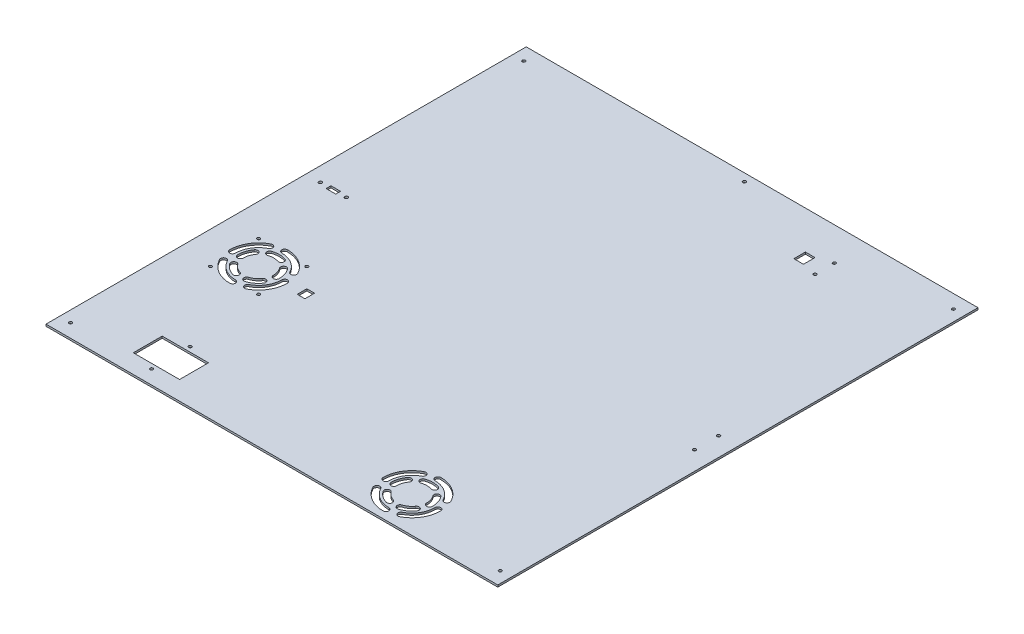
SolidWorks part; units mm, degrees
ref_plane "Alzado" through (0, 0, 0) normal (0, 0, 1) x (1, 0, 0)
ref_plane "Planta" through (0, 0, 0) normal (0, 1, 0) x (1, 0, 0)
ref_plane "Vista lateral" through (0, 0, 0) normal (1, 0, 0) x (0, 0, -1)
sketch "Croquis1" plane through (0, 0, 0) normal (0, 1, 0) x (1, 0, 0)
  line L1 (0, 0) -> (470.5, 0)
  line L2 (0, 0) -> (0, 420)
  line L3 (0, 420) -> (470.5, 420)
  line L4 (470.5, 0) -> (470.5, 420)
  dimension "D1" = 420
  dimension "D2" = 470.5
extrude "Saliente-Extruir1" add sketch "Croquis1" along normal blind 2
sketch "Croquis2" plane through (0, 2, 0) normal (0, 1, 0) x (1, 0, 0)
  line L0 (470.5, 420) -> (0, 420) construction
  line L1 (0, 420) -> (0, 0) construction
  line L2 (235.25, 420) -> (235.25, 0) construction
  line L3 (0, 0) -> (470.5, 0) construction
  line L4 (0, 210) -> (470.5, 210) construction
  line L5 (470.5, 0) -> (470.5, 420) construction
  circle A0 centre (12.5, 405) radius 1.55
  circle A1 centre (458, 405) radius 1.55
  circle A2 centre (458, 15) radius 1.55
  circle A3 centre (12.5, 15) radius 1.55
  dimension "D1" = 3.1
  dimension "D2" = 15
  dimension "D3" = 12.5
extrude "Cortar-Extruir1" cut sketch "Croquis2" against normal up to surface (2 mm away) up to face at (235.25, 0, -210)
sketch "Croquis3" plane through (0, 2, 0) normal (0, 1, 0) x (1, 0, 0)
  line L0 (470, 419.5) -> (0.5, 419.5)
  line L1 (0.5, 419.5) -> (0.5, 0.5)
  line L2 (0.5, 0.5) -> (470, 0.5)
  line L3 (470, 0.5) -> (470, 419.5)
  line L4 (0, 420) -> (0, 0)
  line L5 (0, 0) -> (470.5, 0)
  line L6 (470.5, 0) -> (470.5, 420)
  line L7 (470.5, 420) -> (0, 420)
  line L8 (0, 420) -> (0, 0)
  line L9 (0, 0) -> (470.5, 0)
  line L10 (470.5, 0) -> (470.5, 420)
  line L11 (470.5, 420) -> (0, 420)
  dimension "D1" = 0
  dimension "D2" = 0.5
extrude "Cortar-Extruir2" cut sketch "Croquis3" against normal up to surface (2 mm away) up to face at (12.5, 0, -16.55)
sketch "Croquis4" plane through (0, 2, 0) normal (0, 1, 0) x (1, 0, 0)
  line L0 (0.5, 0.5) -> (470, 0.5) construction
  line L1 (0.5, 419.5) -> (0.5, 0.5) construction
  line L3 (0.5, 419.5) -> (0.5, 0.5) construction
  line L13 (110.5, 201) -> (8.5, 201) construction
  line L14 (110.5, 201) -> (110.5, 125) construction
  line L15 (110.5, 125) -> (8.5, 125) construction
  line L16 (8.5, 201) -> (8.5, 125) construction
  line L17 (59.5, 201) -> (59.5, 125) construction
  line L18 (84.5, 138) -> (34.5, 138) construction
  line L19 (105.5, 105.5) -> (13.5, 105.5) construction
  line L20 (105.5, 105.5) -> (105.5, 220.5) construction
  line L21 (105.5, 220.5) -> (13.5, 220.5) construction
  line L22 (13.5, 105.5) -> (13.5, 220.5) construction
  line L23 (105.5, 105.5) -> (13.5, 220.5) construction
  line L24 (105.5, 220.5) -> (13.5, 105.5) construction
  line L25 (84.5, 138) -> (84.5, 188) construction
  line L26 (84.5, 188) -> (34.5, 188) construction
  line L27 (34.5, 138) -> (34.5, 188) construction
  line L28 (84.5, 138) -> (34.5, 188) construction
  line L29 (84.5, 188) -> (34.5, 138) construction
  line L30 (0.5, 0.5) -> (470, 0.5) construction
  circle A0 centre (343.5, 38) radius 27 construction
  arc A1 (343.5, 65) -> (367.4419, 50.4815) centre (343.5, 38) cw construction
  arc A2 (370.1021, 51.8683) -> (343.5, 68) centre (343.5, 38) ccw
  arc A3 (364.7817, 49.0947) -> (343.5, 62) centre (343.5, 38) ccw
  arc A4 (364.7817, 49.0947) -> (370.1021, 51.8683) centre (367.4419, 50.4815) ccw
  arc A5 (343.5, 68) -> (343.5, 62) centre (343.5, 65) ccw
  arc A6 (354.5947, 16.7183) -> (367.5, 38) centre (343.5, 38) ccw
  arc A7 (354.5947, 16.7183) -> (357.3683, 11.3979) centre (355.9815, 14.0581) ccw
  arc A8 (373.5, 38) -> (367.5, 38) centre (370.5, 38) ccw
  arc A9 (357.3683, 11.3979) -> (373.5, 38) centre (343.5, 38) ccw
  arc A10 (370.5, 38) -> (355.9815, 14.0581) centre (343.5, 38) cw construction
  arc A11 (322.2183, 26.9053) -> (343.5, 14) centre (343.5, 38) ccw
  arc A12 (322.2183, 26.9053) -> (316.8979, 24.1317) centre (319.5581, 25.5185) ccw
  arc A13 (343.5, 8) -> (343.5, 14) centre (343.5, 11) ccw
  arc A14 (316.8979, 24.1317) -> (343.5, 8) centre (343.5, 38) ccw
  arc A15 (343.5, 11) -> (319.5581, 25.5185) centre (343.5, 38) cw construction
  arc A16 (332.4053, 59.2817) -> (319.5, 38) centre (343.5, 38) ccw
  arc A17 (332.4053, 59.2817) -> (329.6317, 64.6021) centre (331.0185, 61.9419) ccw
  arc A18 (313.5, 38) -> (319.5, 38) centre (316.5, 38) ccw
  arc A19 (329.6317, 64.6021) -> (313.5, 38) centre (343.5, 38) ccw
  arc A20 (316.5, 38) -> (331.0185, 61.9419) centre (343.5, 38) cw construction
  circle A21 centre (343.5, 38) radius 18.5 construction
  arc A22 (337.5, 55.5) -> (349.5, 55.5) centre (343.5, 38) cw construction
  arc A23 (350.473, 58.3378) -> (336.527, 58.3378) centre (343.5, 38) ccw
  arc A24 (348.527, 52.6622) -> (338.473, 52.6622) centre (343.5, 38) ccw
  arc A25 (348.527, 52.6622) -> (350.473, 58.3378) centre (349.5, 55.5) ccw
  arc A26 (336.527, 58.3378) -> (338.473, 52.6622) centre (337.5, 55.5) ccw
  arc A27 (358.2894, 49.1141) -> (361.9976, 37.7015) centre (343.5, 38) cw construction
  arc A28 (364.9972, 37.653) -> (360.6877, 50.9164) centre (343.5, 38) ccw
  arc A29 (358.998, 37.7499) -> (355.8911, 47.3118) centre (343.5, 38) ccw
  arc A30 (358.998, 37.7499) -> (364.9972, 37.653) centre (361.9976, 37.7015) ccw
  arc A31 (360.6877, 50.9164) -> (355.8911, 47.3118) centre (358.2894, 49.1141) ccw
  arc A32 (358.6403, 27.3689) -> (348.9321, 20.3155) centre (343.5, 38) cw construction
  arc A33 (349.813, 17.4477) -> (361.0955, 25.645) centre (343.5, 38) ccw
  arc A34 (348.0513, 23.1832) -> (356.1852, 29.0929) centre (343.5, 38) ccw
  arc A35 (348.0513, 23.1832) -> (349.813, 17.4477) centre (348.9321, 20.3155) ccw
  arc A36 (361.0955, 25.645) -> (356.1852, 29.0929) centre (358.6403, 27.3689) ccw
  arc A37 (338.0679, 20.3155) -> (328.3597, 27.3689) centre (343.5, 38) cw construction
  arc A38 (325.9045, 25.645) -> (337.187, 17.4477) centre (343.5, 38) ccw
  arc A39 (330.8148, 29.0929) -> (338.9487, 23.1832) centre (343.5, 38) ccw
  arc A40 (330.8148, 29.0929) -> (325.9045, 25.645) centre (328.3597, 27.3689) ccw
  arc A41 (337.187, 17.4477) -> (338.9487, 23.1832) centre (338.0679, 20.3155) ccw
  arc A42 (325.0024, 37.7015) -> (328.7106, 49.1141) centre (343.5, 38) cw construction
  arc A43 (326.3123, 50.9164) -> (322.0028, 37.653) centre (343.5, 38) ccw
  arc A44 (331.1089, 47.3118) -> (328.002, 37.7499) centre (343.5, 38) ccw
  arc A45 (331.1089, 47.3118) -> (326.3123, 50.9164) centre (328.7106, 49.1141) ccw
  arc A46 (322.0028, 37.653) -> (328.002, 37.7499) centre (325.0024, 37.7015) ccw
  circle A47 centre (84.5, 188) radius 1.55
  circle A48 centre (84.5, 138) radius 1.55
  circle A57 centre (34.5, 138) radius 1.55
  circle A68 centre (34.5, 188) radius 1.55
  circle A69 centre (59.5, 163) radius 27 construction
  arc A84 (59.5, 190) -> (83.4419, 175.4815) centre (59.5, 163) cw construction
  circle A94 centre (458, 405) radius 1.55 construction
  arc A98 (86.1021, 176.8683) -> (59.5, 193) centre (59.5, 163) ccw
  arc A103 (80.7817, 174.0947) -> (59.5, 187) centre (59.5, 163) ccw
  arc A124 (80.7817, 174.0947) -> (86.1021, 176.8683) centre (83.4419, 175.4815) ccw
  arc A129 (59.5, 193) -> (59.5, 187) centre (59.5, 190) ccw
  circle A143 centre (110.5, 201) radius 1.55 construction
  circle A144 centre (8.5, 201) radius 1.55 construction
  circle A145 centre (8.5, 125) radius 1.55 construction
  circle A146 centre (110.5, 125) radius 1.55 construction
  circle A147 centre (105.5, 220.5) radius 1.55 construction
  circle A148 centre (13.5, 220.5) radius 1.55 construction
  circle A149 centre (13.5, 105.5) radius 1.55 construction
  circle A150 centre (105.5, 105.5) radius 1.55 construction
  arc A154 (86.5, 163) -> (71.9815, 139.0581) centre (59.5, 163) cw construction
  arc A159 (73.3683, 136.3979) -> (89.5, 163) centre (59.5, 163) ccw
  arc A164 (70.5947, 141.7183) -> (83.5, 163) centre (59.5, 163) ccw
  circle A165 centre (59.5, 163) radius 18.5 construction
  arc A166 (53.5, 180.5) -> (65.5, 180.5) centre (59.5, 163) cw construction
  arc A167 (66.473, 183.3378) -> (52.527, 183.3378) centre (59.5, 163) ccw
  arc A168 (64.527, 177.6622) -> (54.473, 177.6622) centre (59.5, 163) ccw
  arc A169 (64.527, 177.6622) -> (66.473, 183.3378) centre (65.5, 180.5) ccw
  arc A170 (52.527, 183.3378) -> (54.473, 177.6622) centre (53.5, 180.5) ccw
  arc A171 (70.5947, 141.7183) -> (73.3683, 136.3979) centre (71.9815, 139.0581) ccw
  arc A172 (89.5, 163) -> (83.5, 163) centre (86.5, 163) ccw
  arc A173 (59.5, 136) -> (35.5581, 150.5185) centre (59.5, 163) cw construction
  arc A174 (32.8979, 149.1317) -> (59.5, 133) centre (59.5, 163) ccw
  arc A175 (38.2183, 151.9053) -> (59.5, 139) centre (59.5, 163) ccw
  arc A176 (38.2183, 151.9053) -> (32.8979, 149.1317) centre (35.5581, 150.5185) ccw
  arc A177 (59.5, 133) -> (59.5, 139) centre (59.5, 136) ccw
  arc A178 (32.5, 163) -> (47.0185, 186.9419) centre (59.5, 163) cw construction
  arc A179 (45.6317, 189.6021) -> (29.5, 163) centre (59.5, 163) ccw
  arc A180 (48.4053, 184.2817) -> (35.5, 163) centre (59.5, 163) ccw
  arc A181 (48.4053, 184.2817) -> (45.6317, 189.6021) centre (47.0185, 186.9419) ccw
  arc A182 (29.5, 163) -> (35.5, 163) centre (32.5, 163) ccw
  circle A183 centre (59.5, 163) radius 18.5 construction
  arc A184 (74.2894, 174.1141) -> (77.9976, 162.7015) centre (59.5, 163) cw construction
  arc A185 (80.9972, 162.653) -> (76.6877, 175.9164) centre (59.5, 163) ccw
  arc A186 (74.998, 162.7499) -> (71.8911, 172.3118) centre (59.5, 163) ccw
  arc A187 (74.998, 162.7499) -> (80.9972, 162.653) centre (77.9976, 162.7015) ccw
  arc A188 (76.6877, 175.9164) -> (71.8911, 172.3118) centre (74.2894, 174.1141) ccw
  circle A189 centre (59.5, 163) radius 18.5 construction
  arc A190 (74.6403, 152.3689) -> (64.9321, 145.3155) centre (59.5, 163) cw construction
  arc A191 (65.813, 142.4477) -> (77.0955, 150.645) centre (59.5, 163) ccw
  arc A192 (64.0513, 148.1832) -> (72.1852, 154.0929) centre (59.5, 163) ccw
  arc A193 (64.0513, 148.1832) -> (65.813, 142.4477) centre (64.9321, 145.3155) ccw
  arc A194 (77.0955, 150.645) -> (72.1852, 154.0929) centre (74.6403, 152.3689) ccw
  circle A195 centre (59.5, 163) radius 18.5 construction
  arc A196 (54.0679, 145.3155) -> (44.3597, 152.3689) centre (59.5, 163) cw construction
  arc A197 (41.9045, 150.645) -> (53.187, 142.4477) centre (59.5, 163) ccw
  arc A198 (46.8148, 154.0929) -> (54.9487, 148.1832) centre (59.5, 163) ccw
  arc A199 (46.8148, 154.0929) -> (41.9045, 150.645) centre (44.3597, 152.3689) ccw
  arc A200 (53.187, 142.4477) -> (54.9487, 148.1832) centre (54.0679, 145.3155) ccw
  circle A201 centre (59.5, 163) radius 18.5 construction
  arc A202 (41.0024, 162.7015) -> (44.7106, 174.1141) centre (59.5, 163) cw construction
  arc A203 (42.3123, 175.9164) -> (38.0028, 162.653) centre (59.5, 163) ccw
  arc A204 (47.1089, 172.3118) -> (44.002, 162.7499) centre (59.5, 163) ccw
  arc A205 (47.1089, 172.3118) -> (42.3123, 175.9164) centre (44.7106, 174.1141) ccw
  arc A206 (38.0028, 162.653) -> (44.002, 162.7499) centre (41.0024, 162.7015) ccw
  point P9 (357.5, 61.0868)
  point P19 (366.5868, 24)
  point P26 (329.5, 14.9132)
  point P33 (320.4132, 52)
  point P38 (343.5, 38)
  point P40 (343.5, 56.5)
  point P48 (361.0945, 43.7168)
  point P51 (59.5, 163)
  point P57 (354.374, 23.0332)
  point P64 (332.626, 23.0332)
  point P71 (325.9055, 43.7168)
  point P76 (343.5, 38)
  point P88 (73.5, 186.0868)
  point P100 (82.5868, 149)
  point P107 (45.5, 139.9132)
  point P114 (36.4132, 177)
  point P119 (59.5, 181.5)
  point P125 (302, 221.5)
  point P129 (77.0945, 168.7168)
  point P137 (70.374, 148.0332)
  point P147 (48.626, 148.0332)
  point P157 (41.9055, 168.7168)
  point P171 (59.5, 163)
  point P183 (302, 221.5)
  dimension "D1" = 54
  dimension "D7" = 37
  dimension "D13" = 54
  dimension "D18" = 6
  dimension "D19" = 105
  dimension "D20" = 105
  dimension "D28" = 3.1
  dimension "D16" = 37
  dimension "D2" = 37.5
  dimension "D3" = 343
  dimension "D4" = 28
  dimension "D5" = 6
  dimension "D8" = 12
  dimension "D9" = 6
  dimension "D11" = 50
  dimension "D12" = 50
  dimension "D14" = 28
  dimension "D15" = 6
  dimension "D17" = 12
  dimension "D26" = 102
  dimension "D27" = 76
  dimension "D31" = 92
  dimension "D32" = 115
  dimension "D6" = 4
  dimension "D10" = 5
extrude "Cortar-Extruir3" cut sketch "Croquis4" against normal up to surface (2 mm away) up to face at (12.5, 0, -406.55)
sketch "Croquis5" plane through (0, 0, 0) normal (0, -1, 0) x (1, 0, 0)
  line L0 (120, -35.5) -> (72, -35.5) construction
  line L1 (120, -50.5) -> (72, -50.5)
  line L2 (120, -50.5) -> (120, -20.5)
  line L3 (120, -20.5) -> (72, -20.5)
  line L4 (72, -50.5) -> (72, -20.5)
  line L5 (470, -0.5) -> (470, -419.5) construction
  line L6 (0.5, -0.5) -> (470, -0.5) construction
  circle A1 centre (96, -15.5) radius 1.55
  circle A2 centre (96, -55.5) radius 1.55
  dimension "D3" = 3.1
  dimension "D1" = 48
  dimension "D2" = 30
  dimension "D4" = 5
  dimension "D5" = 24
  dimension "D6" = 350
  dimension "D7" = 20
extrude "Cortar-Extruir4" cut sketch "Croquis5" against normal up to surface (2 mm away) up to face at (326.8437, 2, -43.412)
sketch "Croquis8" plane through (0, 0, 0) normal (0, -1, 0) x (1, 0, 0)
  line L1 (470, -419.5) -> (0.5, -419.5)
  line L2 (470, -419.5) -> (470, -449.5)
  line L3 (470, -449.5) -> (0.5, -449.5)
  line L4 (0.5, -419.5) -> (0.5, -449.5)
  dimension "D1" = 30
extrude "Saliente-Extruir2" add sketch "Croquis8" against normal up to surface (2 mm away) up to face at (96, 2, -57.05)
sketch "Croquis10" plane through (0, 0, 0) normal (0, -1, 0) x (1, 0, 0)
  circle A0 centre (458, -405) radius 1.75
  circle A1 centre (12.5, -405) radius 1.75
  dimension "D1" = 3.5
  dimension "D2" = 3.5
extrude "Saliente-Extruir3" add sketch "Croquis10" against normal up to surface (2 mm away) up to face at (96, 2, -57.05)
sketch "Croquis11" plane through (0, 0, -449.5) normal (0, 0, -1) x (-1, 0, 0)
  line L4 (-0.5, 2) -> (-470, 2)
  line L5 (-470, 2) -> (-470, 0)
  line L6 (-470, 0) -> (-0.5, 0)
  line L7 (-0.5, 0) -> (-0.5, 2)
  line L8 (-0.5, 2) -> (-470, 2)
  line L9 (-470, 2) -> (-470, 0)
  line L10 (-470, 0) -> (-0.5, 0)
  line L11 (-0.5, 0) -> (-0.5, 2)
  dimension "D1" = 0
extrude "Saliente-Extruir4" add sketch "Croquis11" along normal blind 50
sketch "Croquis12" plane through (0, 0, 0) normal (0, -1, 0) x (1, 0, 0)
  line L0 (470, -0.5) -> (470, -499.5) construction
  line L1 (0.5, -499.5) -> (0.5, -0.5) construction
  line L3 (470, -499.5) -> (0.5, -499.5) construction
  circle A0 centre (458, -485) radius 1.55
  circle A1 centre (12.5, -485) radius 1.55
  dimension "D1" = 3.1
  dimension "D2" = 3.1
  dimension "D3" = 12
  dimension "D4" = 12
  dimension "D5" = 14.5
  dimension "D6" = 14.5
extrude "Cortar-Extruir8" cut sketch "Croquis12" against normal up to surface (2 mm away) up to face at (96, 2, -57.05)
sketch "Croquis13" plane through (0, 0, 0) normal (0, -1, 0) x (1, 0, 0)
  line L0 (470, -0.5) -> (470, -499.5) construction
  line L1 (470, -499.5) -> (0.5, -499.5) construction
  line L3 (340, -459.5) -> (330, -459.5)
  line L4 (340, -459.5) -> (340, -447.5)
  line L5 (340, -447.5) -> (330, -447.5)
  line L6 (330, -459.5) -> (330, -447.5)
  circle A0 centre (355, -464.5) radius 1.55
  circle A1 centre (355, -444.5) radius 1.55
  dimension "D1" = 3.1
  dimension "D2" = 20
  dimension "D3" = 115
  dimension "D4" = 35
  dimension "D5" = 10
  dimension "D6" = 12
  dimension "D7" = 40
  dimension "D8" = 140
extrude "Cortar-Extruir9" cut sketch "Croquis13" against normal up to surface (2 mm away) up to face at (458, 2, -486.55)
sketch "Croquis14" plane through (0, 0, 0) normal (0, -1, 0) x (1, 0, 0)
  line L1 (112.5, -168) -> (104.5, -168)
  line L2 (112.5, -168) -> (112.5, -158)
  line L3 (112.5, -158) -> (104.5, -158)
  line L4 (104.5, -168) -> (104.5, -158)
  circle A0 centre (84.5, -188) radius 1.55 construction
  dimension "D1" = 8
  dimension "D2" = 10
  dimension "D3" = 20
  dimension "D4" = 20
extrude "Cortar-Extruir10" cut sketch "Croquis14" against normal up to surface (2 mm away) up to face at (355, 2, -466.05)
sketch "Croquis15" plane through (0, 0, 0) normal (0, -1, 0) x (1, 0, 0)
  line L0 (470, -0.5) -> (470, -499.5) construction
  line L2 (470, -499.5) -> (0.5, -499.5) construction
  circle A0 centre (450, -249.5) radius 1.6
  circle A1 centre (450, -224.5) radius 1.6
  dimension "D1" = 3.2
  dimension "D2" = 25
  dimension "D3" = 20
  dimension "D4" = 250
extrude "Cortar-Extruir11" cut sketch "Croquis15" against normal up to surface (2 mm away) up to face at (108.5, 2, -163)
sketch "Croquis16" plane through (0, 0, 0) normal (0, -1, 0) x (1, 0, 0)
  line L4 (0.5, -0.5) -> (470, -0.5) construction
  line L5 (0.5, -499.5) -> (0.5, -0.5) construction
  line L6 (470, -0.5) -> (470, -499.5) construction
  line L7 (470, -499.5) -> (0.5, -499.5) construction
  line L8 (1, -1) -> (1, -499)
  line L9 (1, -499) -> (469.5, -499)
  line L10 (469.5, -499) -> (469.5, -1)
  line L11 (469.5, -1) -> (1, -1)
  line L12 (1, -1) -> (1, -499)
  line L13 (1, -499) -> (469.5, -499)
  line L14 (469.5, -499) -> (469.5, -1)
  line L15 (469.5, -1) -> (1, -1)
  line L16 (0.5, -0.5) -> (470, -0.5)
  line L17 (0.5, -499.5) -> (0.5, -0.5)
  line L18 (470, -0.5) -> (470, -499.5)
  line L19 (470, -499.5) -> (0.5, -499.5)
  dimension "D1" = 0.5
extrude "Cortar-Extruir12" cut sketch "Croquis16" against normal up to surface (2 mm away) up to face at (450, 2, -251.1)
sketch "Croquis17" plane through (0, 2, 0) normal (0, 1, 0) x (1, 0, 0)
  line L0 (469.5, 499) -> (1, 499) construction
  line L1 (1, 499) -> (1, 1) construction
  circle A0 centre (235.25, 491) radius 1.6
  dimension "D1" = 3.2
  dimension "D2" = 8
  dimension "D3" = 234.25
extrude "Cortar-Extruir13" cut sketch "Croquis17" against normal up to surface (2 mm away) up to face at (12.5, 0, -16.55)
sketch "Croquis18" plane through (0, 0, 0) normal (0, -1, 0) x (1, 0, 0)
  line L0 (34.5, -270.5) -> (16, -270.5) construction
  line L1 (34.5, -273) -> (24.5, -273)
  line L2 (34.5, -273) -> (34.5, -268)
  line L3 (34.5, -268) -> (24.5, -268)
  line L4 (24.5, -273) -> (24.5, -268)
  line L5 (34.5, -270.5) -> (43, -270.5) construction
  line L6 (29.5, -273) -> (29.5, -268) construction
  line L7 (1, -1) -> (1, -499) construction
  line L9 (72, -50.5) -> (120, -50.5) construction
  circle A0 centre (16, -270.5) radius 1.65
  circle A1 centre (43, -270.5) radius 1.65
  point P15 (28.975, -499)
  dimension "D3" = 3.3
  dimension "D4" = 3.3
  dimension "D1" = 10
  dimension "D2" = 5
  dimension "D5" = 27
  dimension "D6" = 13.5
  dimension "D7" = 15
  dimension "D8" = 220
extrude "Cortar-Extruir14" cut sketch "Croquis18" against normal up to surface (2 mm away) up to face at (235.25, 2, -489.4)
